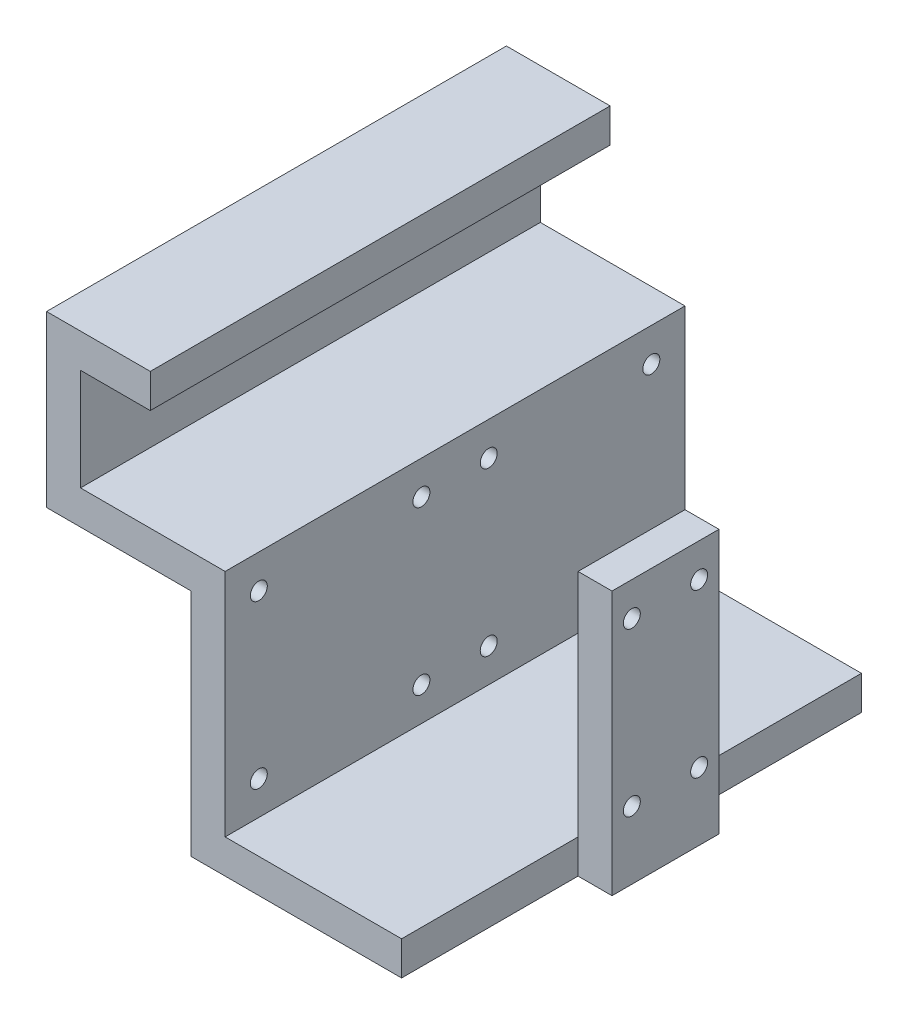
SolidWorks part; units mm, degrees
ref_plane "Front Plane" through (0, 0, 0) normal (0, 0, 1) x (1, 0, 0)
ref_plane "Top Plane" through (0, 0, 0) normal (0, 1, 0) x (1, 0, 0)
ref_plane "Right Plane" through (0, 0, 0) normal (1, 0, 0) x (0, 0, -1)
sketch "Sketch1" plane through (0, 0, 0) normal (0, 0, 1) x (1, 0, 0)
  line L0 (-6.35, -27.85) -> (-6.35, 15.15)
  line L1 (-6.35, 15.15) -> (-33.4, 15.15)
  line L2 (-33.4, 15.15) -> (-33.4, 46.9)
  line L3 (-33.4, 46.9) -> (-14, 46.9)
  line L4 (-14, 46.9) -> (-14, 40.55)
  line L5 (-14, 40.55) -> (-27.05, 40.55)
  line L6 (-27.05, 40.55) -> (-27.05, 21.5)
  line L7 (-27.05, 21.5) -> (0, 21.5)
  line L8 (0, 21.5) -> (0, -21.5)
  line L9 (0, -21.5) -> (33, -21.5)
  line L12 (33, -21.5) -> (33, -27.85)
  line L13 (33, -27.85) -> (-6.35, -27.85)
  line L14 (-27.05, 40.55) -> (11.05, 40.55) construction
  line L15 (-27.05, 40.55) -> (-33.4, 46.9) construction
  line L16 (-27.05, 21.5) -> (-33.4, 15.15) construction
  line L17 (-6.35, 15.15) -> (0, 21.5) construction
  line L18 (0, -21.5) -> (-6.35, -27.85) construction
  line L20 (-27.05, 21.5) -> (-27.05, 40.55) construction
  line L21 (-27.05, 21.5) -> (277.75, 21.5) construction
  line L22 (33, 18.9156) -> (33, -19.0795) construction
  line L23 (33, -21.5) -> (0, -21.5) construction
  line L25 (-14, 43.09) -> (-14, 48.9) construction
  point P23 (-14.4596, 40.55)
  dimension "D1" = 6.35
extrude "Boss-Extrude1" add sketch "Sketch1" against normal up to surface (86 mm away) contours L6 L7 L8 L9 L12 L13 L0 L1 L2 L3 L4 L5
sketch "Sketch2" plane through (33, 0, 0) normal (1, 0, 0) x (0, 0, -1)
  line L0 (86, -27.85) -> (0, -27.85) construction
  line L1 (33, -27.85) -> (53, -27.85)
  line L2 (33, -27.85) -> (33, 21.5)
  line L3 (33, 21.5) -> (53, 21.5)
  line L4 (53, -27.85) -> (53, 21.5)
  line L5 (33, -27.85) -> (53, 21.5) construction
  line L6 (33, 21.5) -> (53, -27.85) construction
  line L7 (86, 21.5) -> (0, 21.5) construction
  circle A0 centre (21.5, 0) radius 11.5 construction
  circle A1 centre (64.5, 0) radius 11.5 construction
  point P4 (43, -3.175)
extrude "Boss-Extrude2" add sketch "Sketch2" along normal blind 6.35
sketch "Sketch3" plane through (39.35, 0, 0) normal (1, 0, 0) x (0, 0, -1)
  line L0 (0, 15.2058) -> (6.2942, 15.2058) construction
  line L1 (0, 21.5) -> (0, -21.5) construction
  line L2 (36.7058, 15.2058) -> (43, 15.2058) construction
  line L3 (43, 15.2058) -> (49.2942, 15.2058) construction
  line L4 (53, 21.5) -> (33, 21.5) construction
  circle A0 centre (6.2942, -15.2058) radius 1.5875
  circle A1 centre (6.2942, 15.2058) radius 1.5875
  circle A2 centre (79.7058, -15.2058) radius 1.5875
  circle A3 centre (79.7058, 15.2058) radius 1.5875
  circle A4 centre (49.2942, -15.2058) radius 1.5875
  circle A5 centre (49.2942, 15.2058) radius 1.5875
  circle A6 centre (36.7058, -15.2058) radius 1.5875
  circle A7 centre (36.7058, 15.2058) radius 1.5875
  point P23 (43, 21.5)
  point P24 (0, 0)
  point P26 (0, 0)
  point P29 (0, 0)
  point P30 (0, 0)
  point P31 (0, 0)
  dimension "D1" = 3.175
extrude "Cut-Extrude1" cut sketch "Sketch3" against normal blind 57.15 contours A0 | A5 | A4 | A2 | A3 | A1 | A6 | A7 region at (39.35, -15.2058, -6.2942) region at (39.35, -15.2058, -79.7058) region at (39.35, 15.2058, -79.7058) region at (39.35, -15.2058, -49.2942) region at (39.35, 15.2058, -49.2942)
